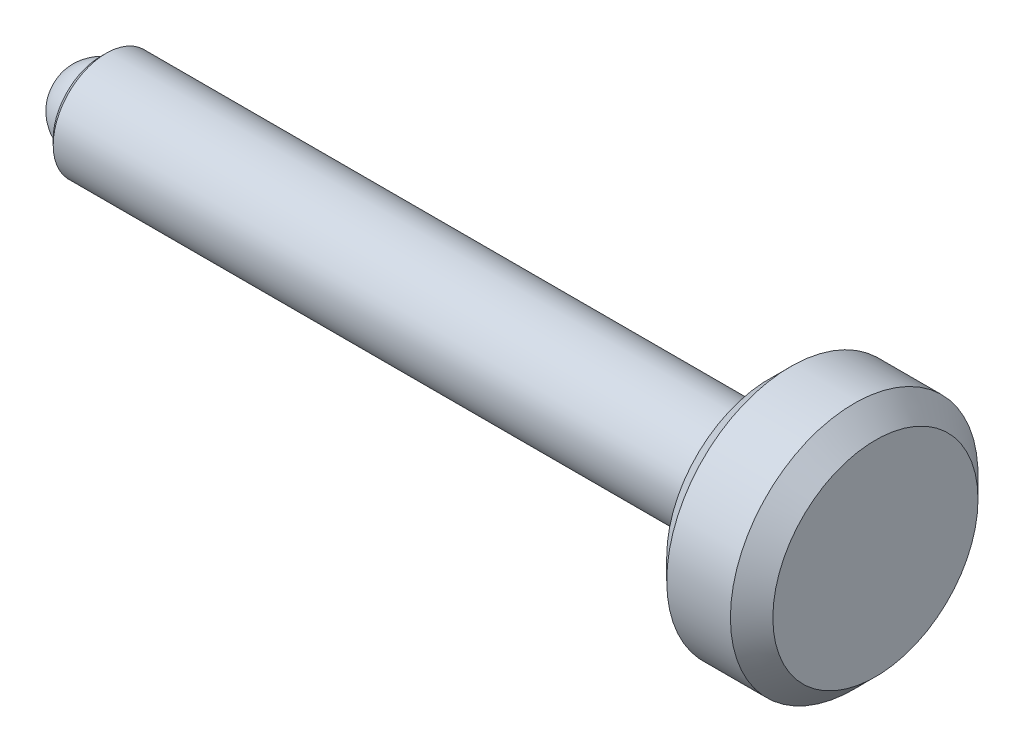
SolidWorks part; units mm, degrees
ref_plane "前视基准面" through (0, 0, 0) normal (0, 0, 1) x (1, 0, 0)
ref_plane "上视基准面" through (0, 0, 0) normal (0, 1, 0) x (1, 0, 0)
ref_plane "右视基准面" through (0, 0, 0) normal (1, 0, 0) x (0, 0, -1)
ref_plane "基准面4" through (23, 0, 0) normal (1, 0, 0) x (0, 0, -1)
ref_plane "基准面5" through (5.75, 0, 0) normal (1, 0, 0) x (0, 0, -1)
ref_plane "基准面6" through (13.8, 0, 0) normal (1, 0, 0) x (0, 0, -1)
sketch "草图1" plane through (0, 0, 0) normal (0, 0, 1) x (1, 0, 0)
  line L0 (1.1, 1.1) -> (1.1, 1.3465)
  line L1 (1.1, 1.3465) -> (1.2535, 1.5)
  line L2 (1.2535, 1.5) -> (19.1, 1.5)
  line L3 (19.1, 1.5) -> (19.1, 1.3465)
  line L4 (19.1, 1.3465) -> (20, 1.3465)
  line L5 (20, 1.3465) -> (20, 2.9)
  line L6 (20, 2.9) -> (20.6, 3.5)
  line L7 (20.6, 3.5) -> (22.4, 3.5)
  line L8 (22.4, 3.5) -> (23, 2.9)
  line L9 (23, 2.9) -> (23, 0)
  line L10 (23, 0) -> (0, 0)
  line L11 (23, 0) -> (0, 0) construction
  arc A0 (0, 0) -> (1.1, 1.1) centre (1.1, 0) cw
revolve "旋转1" add sketch "草图1" angle 360 about L11 reverse direction yes
cosmetic thread "装饰螺纹线1" parameters "D1"=18, "D2"=2.693
ref_plane "基准面7" through (12, 0, 0) normal (1, 0, 0) x (0, 0, -1)
ref_plane "rscrew_to_rnut XY" through (5.75, 0, 0) normal (1, 0, 0) x (0, 0, -1)
ref_plane "rscrew_to_rnut XZ" through (0, 0, 0) normal (0, -1, 0) x (-1, 0, 0)
ref_plane "rscrew_to_rnut YZ" through (0, 0, 0) normal (0, 0, -1) x (-1, 0, 0)
ref_axis "rscrew_to_rnut X" through (5.75, 0, 80.9) along (0, 0, -1)
ref_axis "rscrew_to_rnut Y" through (5.75, -50, 0) along (0, 1, 0)
ref_axis "rscrew_to_rnut Z" through (80.9, 0, 0) along (-1, 0, 0)
sketch3d "rscrew_to_rnut"
  point P0 (5.75, 0, 0)
ref_plane "mnscrew_to_mnnut XY" through (13.8, 0, 0) normal (-1, 0, 0) x (0, 0, 1)
ref_plane "mnscrew_to_mnnut XZ" through (0, 0, 0) normal (0, 1, 0) x (1, 0, 0)
ref_plane "mnscrew_to_mnnut YZ" through (0, 0, 0) normal (0, 0, -1) x (-1, 0, 0)
ref_axis "mnscrew_to_mnnut X" through (13.8, 0, 80.9) along (0, 0, -1)
ref_axis "mnscrew_to_mnnut Y" through (13.8, 50, 0) along (0, -1, 0)
ref_axis "mnscrew_to_mnnut Z" through (-80.9, 0, 0) along (1, 0, 0)
sketch3d "mnscrew_to_mnnut"
  point P0 (13.8, 0, 0)
ref_plane "1 XY" through (12, 0, 0) normal (1, 0, 0) x (0, 0, -1)
ref_plane "1 XZ" through (0, 0, 0) normal (0, -1, 0) x (-1, 0, 0)
ref_plane "1 YZ" through (0, 0, 0) normal (0, 0, -1) x (-1, 0, 0)
ref_axis "1 X" through (12, 0, 80.9) along (0, 0, -1)
ref_axis "1 Y" through (12, -50, 0) along (0, 1, 0)
ref_axis "1 Z" through (80.9, 0, 0) along (-1, 0, 0)
sketch3d "1"
  point P0 (12, 0, 0)
ref_plane "to_stage XY" through (0, 0, 0) normal (1, 0, 0) x (0, 0, -1)
ref_plane "to_stage XZ" through (0, 0, 0) normal (0, -1, 0) x (-1, 0, 0)
ref_plane "to_stage YZ" through (0, 0, 0) normal (0, 0, -1) x (-1, 0, 0)
ref_axis "to_stage X" through (0, 0, 80.9) along (0, 0, -1)
ref_axis "to_stage Y" through (0, -50, 0) along (0, 1, 0)
ref_axis "to_stage Z" through (80.9, 0, 0) along (-1, 0, 0)
sketch3d "to_stage"
  point P0 (0, 0, 0)
